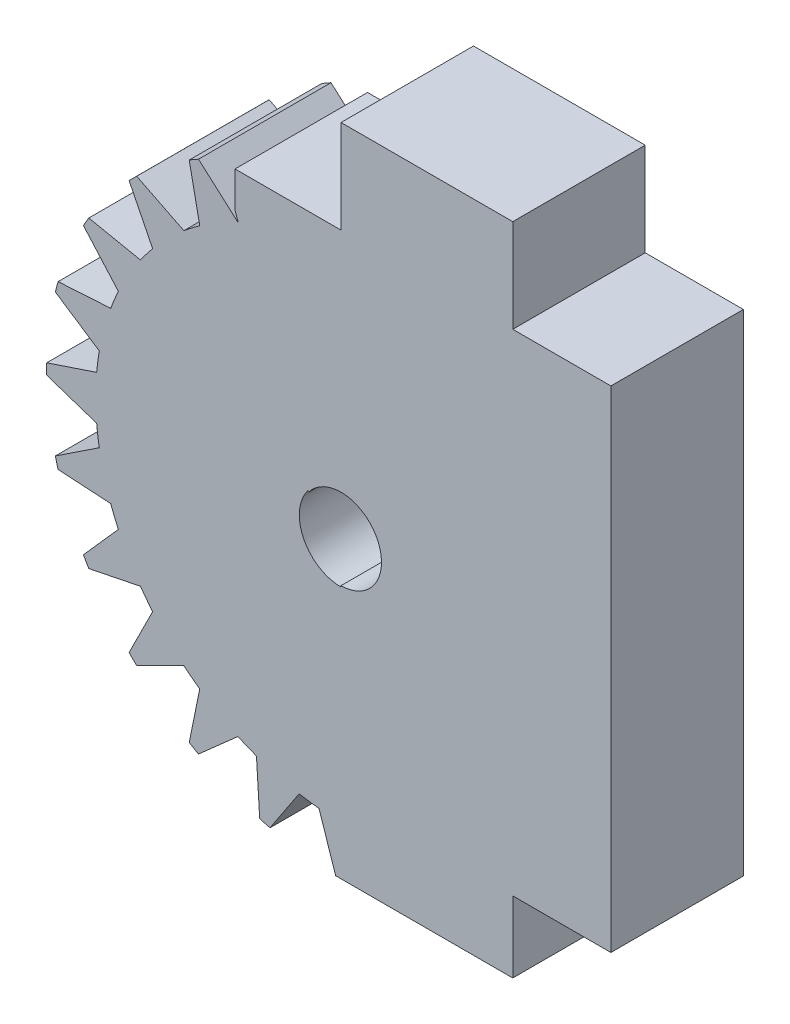
SolidWorks part; units mm, degrees
ref_plane "Front Plane" through (0, 0, 0) normal (0, 0, 1) x (1, 0, 0)
ref_plane "Top Plane" through (0, 0, 0) normal (0, 1, 0) x (1, 0, 0)
ref_plane "Right Plane" through (0, 0, 0) normal (1, 0, 0) x (0, 0, -1)
sketch "Sketch1" plane through (0, 0, 0) normal (0, 0, 1) x (1, 0, 0)
  circle A0 centre (0, 0) radius 10
  dimension "D1" = 20
extrude "Boss-Extrude1" add sketch "Sketch1" along normal blind 5.4
sketch "Sketch2" plane through (0, 0, 0) normal (0, 0, 1) x (1, 0, 0)
  line L2 (0, 12.65) -> (-0.9, 9.9594)
  line L3 (0, 12.65) -> (0.9, 9.9594)
  arc A0 (0.9, 9.9594) -> (-0.9, 9.9594) centre (0, 0) ccw
  dimension "D1" = 20
  dimension "D3" = 2.8371
  dimension "D4" = 1.8
extrude "Boss-Extrude2" add sketch "Sketch2" along normal blind 5.4
pattern_circular "CirPattern1" count 24 every 15 about axis through (0, 0, 5.4) along (0, 0, 1) of "Boss-Extrude2"
sketch "Sketch3" plane through (0, 0, 0) normal (0, 0, 1) x (1, 0, 0)
  circle A0 centre (0, 0) radius 12
  circle A1 centre (0, 0) radius 12.65
  dimension "D1" = 24
  dimension "D2" = 25.3
extrude "Cut-Extrude1" cut sketch "Sketch3" along normal blind 6
sketch "Sketch4" plane through (0, 0, 0) normal (0, 0, 1) x (1, 0, 0)
  line L0 (0, 0) -> (0, -12)
  line L1 (0, 0) -> (-20.8486, 0) construction
  line L2 (0, 0) -> (-3.8268, -9.2388) construction
  line L3 (-3.8268, 9.2388) -> (-4.5922, 11.0866)
  line L4 (-3.8268, -9.2388) -> (-4.5922, -11.0866) construction
  line L5 (0, 0) -> (-3.8268, 9.2388)
  arc A0 (0, -12) -> (-4.5922, 11.0866) centre (0, 0) ccw
  arc A2 (-4.2003, -9.0751) -> (-3.447, -9.3871) centre (0, 0) ccw construction
  dimension "D1" = 22.5
extrude "Cut-Extrude2" cut sketch "Sketch4" along normal blind 6
sketch "Sketch5" plane through (0, 0, 0) normal (0, 0, 1) x (1, 0, 0)
  circle A0 centre (0, 0) radius 1.7
  dimension "D1" = 3.4
extrude "Cut-Extrude3" cut sketch "Sketch5" along normal blind 6
sketch "Sketch6" plane through (0, 0, 0) normal (0, 0, 1) x (1, 0, 0)
  line L0 (0, 65.7933) -> (0, 76.1433) construction
  line L1 (-40.712, 32.0716) -> (40.712, 32.0716) construction
  line L2 (-4.32, 9.4388) -> (-4.32, 10.9)
  line L3 (11, 73.2433) -> (7, 73.2433) construction
  line L4 (-1.3286, 0.9785) -> (-4.32, 9.4388)
  line L5 (7, 73.2433) -> (7, 76.1433) construction
  line L6 (11, 53.2433) -> (11, 73.2433) construction
  line L7 (11, 53.2433) -> (7, 53.2433) construction
  line L8 (7, 53.2433) -> (7, 49.4433) construction
  line L9 (0, 10.9) -> (0, 14.7)
  line L10 (0, 76.1433) -> (7, 76.1433) construction
  line L11 (-4.32, 10.9) -> (0, 10.9)
  line L12 (7, 14.7) -> (0, 14.7)
  line L13 (0, -12) -> (7, -12)
  line L14 (7, 49.4433) -> (0, 49.4433) construction
  line L15 (-4.32, 53.2433) -> (0, 53.2433) construction
  line L16 (0, 53.2433) -> (0, 49.4433) construction
  line L17 (-1.3286, 63.1648) -> (-4.32, 54.7045) construction
  line L18 (-4.32, 54.7045) -> (-4.32, 53.2433) construction
  line L19 (7, 10.9) -> (7, 14.7)
  line L20 (11, 10.9) -> (7, 10.9)
  line L21 (11, 10.9) -> (11, -9.1)
  line L22 (7, -9.1) -> (7, -12)
  line L23 (11, -9.1) -> (7, -9.1)
  line L24 (0, -1.65) -> (0, -12)
  line L25 (0, 64.1433) -> (0, 0) construction
  arc A0 (-1.3286, 63.1648) -> (0, 65.7933) centre (0, 64.1433) ccw construction
  arc A1 (-1.3286, 0.9785) -> (0, -1.65) centre (0, 0) cw
  dimension "D3" = 1.65
  dimension "D4" = 20
  dimension "D5" = 4
  dimension "D11" = 4
  dimension "D2" = 2.9
  dimension "D6" = 7
  dimension "D7" = 3.8
  dimension "D8" = 7
  dimension "D9" = 4.32
extrude "Boss-Extrude3" add sketch "Sketch6" along normal blind 5.4
sketch "Sketch7" [suppressed] plane through (0, 0, 6) normal (0, 0, 1) x (1, 0, 0)
  line L0 (-0.2181, 11.998) -> (7, 12)
  line L1 (7, 12) -> (7, 9.9045)
  line L2 (7, 9.9045) -> (11, 9.9045)
  line L3 (11, 9.9045) -> (11, -10.0955)
  line L4 (11, -10.0955) -> (7, -10.0955)
  line L5 (7, -10.0955) -> (7, -13.0955)
  line L6 (7, -13.0955) -> (0, -13.0955)
  line L7 (0, -13.0955) -> (0, -10.0955)
  line L8 (0, -10.0955) -> (-3.8268, -10.0955)
  line L9 (-3.8268, -10.0955) -> (-3.8268, -9.2388)
  line L10 (-0.2181, 11.998) -> (-0.9, 9.9594)
  line L11 (-1.7084, 9.853) -> (-2.8947, 11.6456)
  line L12 (-2.8947, 11.6456) -> (-3.316, 11.5328)
  line L13 (-3.316, 11.5328) -> (-3.447, 9.3871)
  line L14 (-4.2003, 9.0751) -> (-5.8101, 10.4996)
  line L15 (-5.8101, 10.4996) -> (-6.1879, 10.2815)
  line L16 (-6.1879, 10.2815) -> (-5.7591, 8.1751)
  line L17 (-6.406, 7.6788) -> (-8.3297, 8.6381)
  line L18 (-8.3297, 8.6381) -> (-8.6381, 8.3297)
  line L19 (-8.6381, 8.3297) -> (-7.6788, 6.406)
  line L20 (-8.1751, 5.7591) -> (-10.2815, 6.1879)
  line L21 (-10.2815, 6.1879) -> (-10.4996, 5.8101)
  line L22 (-10.4996, 5.8101) -> (-9.0751, 4.2003)
  line L23 (-9.3871, 3.447) -> (-11.5328, 3.316)
  line L24 (-11.5328, 3.316) -> (-11.6456, 2.8947)
  line L25 (-11.6456, 2.8947) -> (-9.853, 1.7084)
  line L26 (-9.9594, 0.9) -> (-11.998, 0.2181)
  line L27 (-11.998, 0.2181) -> (-11.998, -0.2181)
  line L28 (-11.998, -0.2181) -> (-9.9594, -0.9)
  line L29 (-9.853, -1.7084) -> (-11.6456, -2.8947)
  line L30 (-11.6456, -2.8947) -> (-11.5328, -3.316)
  line L31 (-11.5328, -3.316) -> (-9.3871, -3.447)
  line L32 (-9.0751, -4.2003) -> (-10.4996, -5.8101)
  line L33 (-10.4996, -5.8101) -> (-10.2815, -6.1879)
  line L34 (-10.2815, -6.1879) -> (-8.1751, -5.7591)
  line L35 (-7.6788, -6.406) -> (-8.6381, -8.3297)
  line L36 (-7.6788, -6.406) -> (-8.6381, -8.3297) construction
  line L37 (-8.6381, -8.3297) -> (-8.3297, -8.6381)
  line L38 (-8.3297, -8.6381) -> (-6.406, -7.6788)
  line L39 (-5.7591, -8.1751) -> (-6.1879, -10.2815)
  line L40 (-6.1879, -10.2815) -> (-5.8101, -10.4996)
  line L41 (-5.8101, -10.4996) -> (-4.2003, -9.0751)
  circle A0 centre (0, 0) radius 1.5
  arc A1 (-0.9, 9.9594) -> (-1.7084, 9.853) centre (0, 0) ccw
  arc A2 (-3.447, 9.3871) -> (-4.2003, 9.0751) centre (0, 0) ccw
  arc A3 (-5.7591, 8.1751) -> (-6.406, 7.6788) centre (0, 0) ccw
  arc A4 (-7.6788, 6.406) -> (-8.1751, 5.7591) centre (0, 0) ccw
  arc A5 (-9.0751, 4.2003) -> (-9.3871, 3.447) centre (0, 0) ccw
  arc A6 (-9.853, 1.7084) -> (-9.9594, 0.9) centre (0, 0) ccw
  arc A7 (-4.2003, -9.0751) -> (-3.8268, -9.2388) centre (0, 0) ccw
  arc A8 (-6.406, -7.6788) -> (-5.7591, -8.1751) centre (0, 0) ccw
  arc A9 (-8.1751, -5.7591) -> (-7.6788, -6.406) centre (0, 0) ccw
  arc A10 (-9.3871, -3.447) -> (-9.0751, -4.2003) centre (0, 0) ccw
  arc A11 (-9.9594, -0.9) -> (-9.853, -1.7084) centre (0, 0) ccw
equation "\"D2@Sketch6\"= 2.1 + \"tol2@parametersSketch@prostheticParameters.SLDPRT\" * 2"
equation "\"D7@Sketch6\"= 3 + \"tol2@parametersSketch@prostheticParameters.SLDPRT\" * 2"
equation "\"D1@Boss-Extrude3\" = 5.8 - \"tol2@parametersSketch@prostheticParameters.SLDPRT\""
equation "\"D1@Boss-Extrude1\" = 5.8 - \"tol2@parametersSketch@prostheticParameters.SLDPRT\""
equation "\"D1@Boss-Extrude2\"= 5.8 - \"tol2@parametersSketch@prostheticParameters.SLDPRT\""
equation "\"D1@Sketch5\"= 3 + \"tol1@parametersSketch@prostheticParameters.SLDPRT\""
